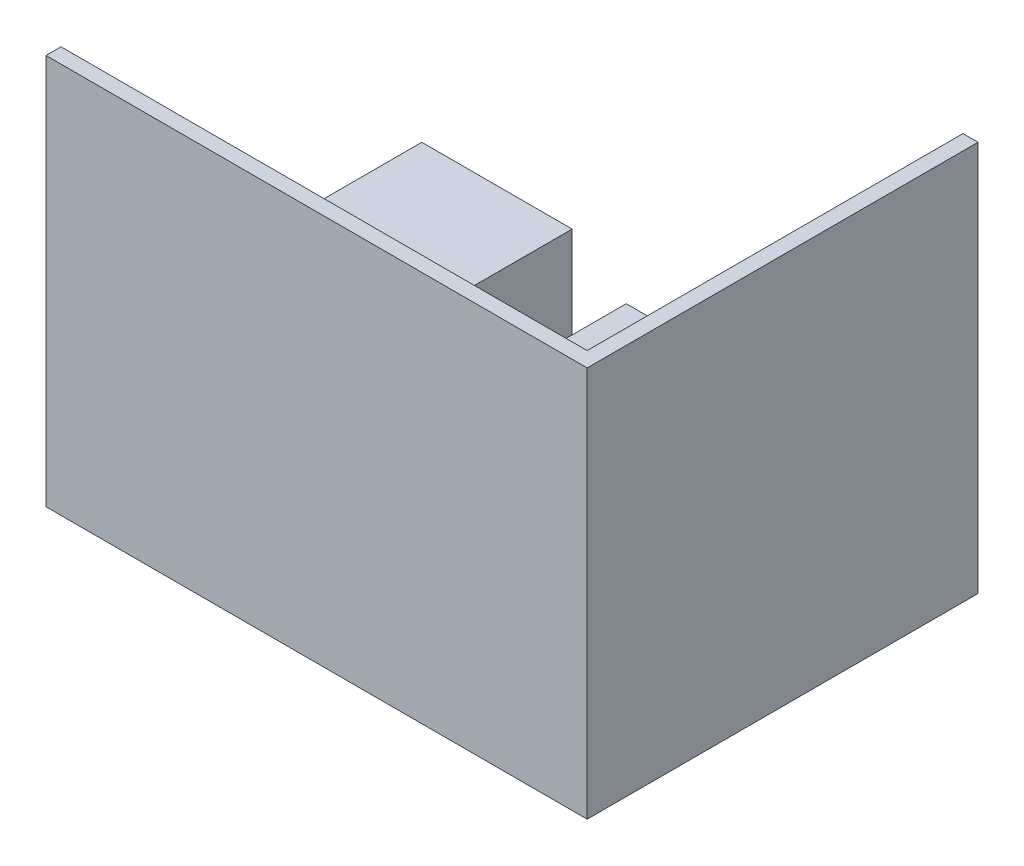
SolidWorks part; units mm, degrees
ref_plane "Front Plane" through (0, 0, 0) normal (0, 0, 1) x (1, 0, 0)
ref_plane "Top Plane" through (0, 0, 0) normal (0, 1, 0) x (1, 0, 0)
ref_plane "Right Plane" through (0, 0, 0) normal (1, 0, 0) x (0, 0, -1)
sketch "Sketch1" plane through (0, 0, 0) normal (0, 1, 0) x (1, 0, 0)
  line L1 (0, 2600) -> (3600, 2600)
  line L2 (0, 2600) -> (0, 0)
  line L3 (0, 0) -> (3600, 0)
  line L4 (3600, 2600) -> (3600, 0)
  point P4 (0, 0)
  dimension "D1" = 3600
  dimension "D2" = 2600
extrude "Boss-Extrude1" add sketch "Sketch1" along normal blind 100
sketch "Sketch2" plane through (0, 100, 0) normal (0, 1, 0) x (1, 0, 0)
  line L1 (0, 0) -> (3600, 0) construction
  line L4 (0, 2600) -> (0, 0) construction
  line L7 (3600, 2600) -> (3600, 0)
  line L8 (3600, 0) -> (0, 0)
  line L9 (0, 0) -> (0, 100)
  line L10 (0, 100) -> (3500, 100)
  line L12 (3500, 100) -> (3500, 2600)
  line L13 (3600, 2600) -> (0, 2600) construction
  line L14 (3500, 2600) -> (3600, 2600)
  point P5 (3500, 0)
  point P6 (3589.9493, 0)
  dimension "D1" = 100
  dimension "D3" = 100
extrude "Boss-Extrude2" add sketch "Sketch2" along normal blind 2500
sketch "Sketch4" plane through (0, 100, 0) normal (0, 1, 0) x (1, 0, 0)
  line L1 (3485, 1000) -> (1510, 1000)
  line L2 (3485, 1000) -> (3485, 1700)
  line L3 (3485, 1700) -> (1510, 1700)
  line L4 (1510, 1000) -> (1510, 1700)
  line L5 (0, 0) -> (3600, 0) construction
  line L7 (3500, 2600) -> (3500, 100) construction
  dimension "D1" = 1975
  dimension "D2" = 700
  dimension "D3" = 1000
  dimension "D4" = 15
extrude "Boss-Extrude3" add sketch "Sketch4" along normal blind 850
sketch "Sketch5" plane through (0, 100, 0) normal (0, 1, 0) x (1, 0, 0)
  line L1 (0, 0) -> (1000, 0)
  line L2 (0, 0) -> (0, 2500)
  line L3 (0, 2500) -> (1000, 2500)
  line L4 (1000, 0) -> (1000, 2500)
  line L5 (0, 2600) -> (0, 100) construction
  line L6 (3500, 2600) -> (0, 2600) construction
  line L7 (0, 0) -> (3600, 0) construction
  point P7 (0, 0)
  dimension "D1" = 1000
  dimension "D2" = 100
extrude "Boss-Extrude4" add sketch "Sketch5" along normal blind 750
sketch "Sketch6" plane through (0, 100, 0) normal (0, 1, 0) x (1, 0, 0)
  line L0 (3485, 1700) -> (1510, 1700) construction
  line L1 (1610, 1750) -> (2310, 1750)
  line L2 (1610, 1750) -> (1610, 2250)
  line L3 (1610, 2250) -> (2310, 2250)
  line L4 (2310, 1750) -> (2310, 2250)
  line L6 (1510, 1700) -> (1510, 1000) construction
  dimension "D1" = 500
  dimension "D2" = 700
  dimension "D3" = 50
  dimension "D4" = 100
extrude "Boss-Extrude5" add sketch "Sketch6" along normal blind 750
sketch "Sketch7" plane through (0, 100, 0) normal (0, 1, 0) x (1, 0, 0)
  line L0 (1610, 1750) -> (1610, 1700) construction
  line L1 (1610, 950) -> (2310, 950)
  line L2 (1610, 950) -> (1610, 450)
  line L3 (1610, 450) -> (2310, 450)
  line L4 (2310, 950) -> (2310, 450)
  line L5 (1610, 2250) -> (2310, 2250) construction
  line L6 (1610, 2250) -> (1610, 1750) construction
  line L7 (1610, 1750) -> (2310, 1750) construction
  line L8 (2310, 2250) -> (2310, 1750) construction
  line L9 (3485, 1700) -> (1510, 1700) construction
  line L10 (1610, 950) -> (1610, 1000) construction
  line L11 (1510, 1000) -> (3485, 1000) construction
extrude "Boss-Extrude6" add sketch "Sketch7" along normal blind 750
